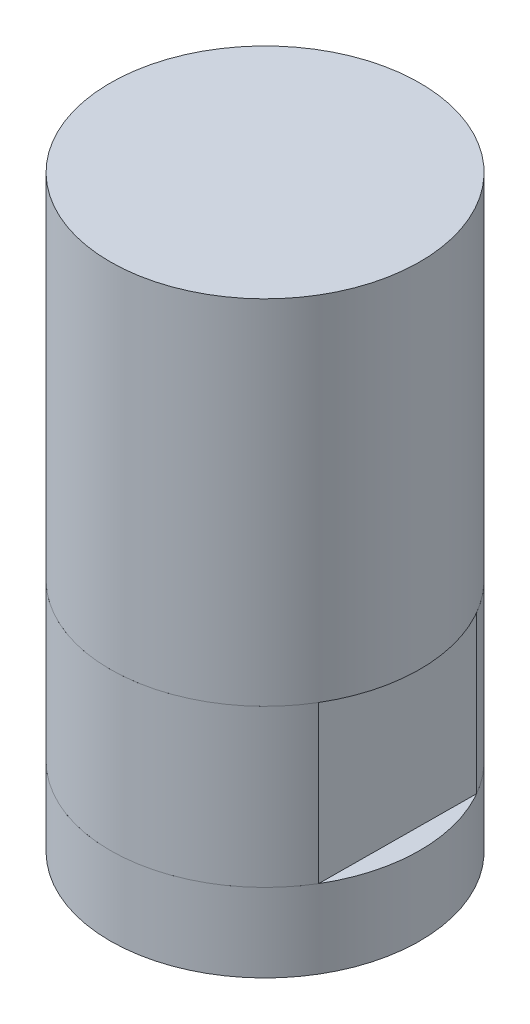
SolidWorks part; units mm, degrees
ref_plane "Front Plane" through (0, 0, 0) normal (0, 0, 1) x (1, 0, 0)
ref_plane "Top Plane" through (0, 0, 0) normal (0, 1, 0) x (1, 0, 0)
ref_plane "Right Plane" through (0, 0, 0) normal (1, 0, 0) x (0, 0, -1)
sketch "Sketch1" plane through (0, 0, 0) normal (0, 1, 0) x (1, 0, 0)
  circle A0 centre (0, 0) radius 3.95
  dimension "D1" = 7.9
extrude "Boss-Extrude1" add sketch "Sketch1" along normal blind 2 contours A0
sketch "Sketch3" plane through (0, 2, 0) normal (0, 1, 0) x (1, 0, 0)
  line L2 (-2.0256, 3.3911) -> (1.9744, 3.4212)
  line L3 (3.4212, 1.9744) -> (3.3911, -2.0256)
  arc A2 (-2.0256, 3.3911) -> (3.3911, -2.0256) centre (0, 0) ccw
  arc A3 (3.4212, 1.9744) -> (1.9744, 3.4212) centre (0, 0) ccw
  point P3 (3.4212, 1.9744)
  point P4 (3.3911, -2.0256)
  point P5 (1.9744, 3.4212)
  point P6 (-2.0256, 3.3911)
  dimension "D3" = 3.95
  dimension "D1" = 4
  dimension "D2" = 4
extrude "Boss-Extrude2" add sketch "Sketch3" along normal blind 4
sketch "Sketch4" plane through (0, 6, 0) normal (0, 1, 0) x (1, 0, 0)
  circle A0 centre (0, 0) radius 3.95
  dimension "D1" = 7.9
extrude "Boss-Extrude3" add sketch "Sketch4" along normal blind 2
sketch "Sketch5" plane through (0, 8, 0) normal (0, 1, 0) x (1, 0, 0)
  line L0 (-2.2, 0) -> (1.6762, 0) construction
  line L2 (1.6762, 1.4249) -> (1.6762, -1.4249)
  arc A1 (1.6762, 1.4249) -> (1.6762, -1.4249) centre (0, 0) ccw
  dimension "D1" = 2.2
extrude "Cut-Extrude1" cut sketch "Sketch5" against normal through all
sketch "Sketch6" plane through (0, 8, 0) normal (0, 1, 0) x (1, 0, 0)
  circle A0 centre (0, 0) radius 3.95
extrude "Boss-Extrude4" add sketch "Sketch6" along normal blind 7
